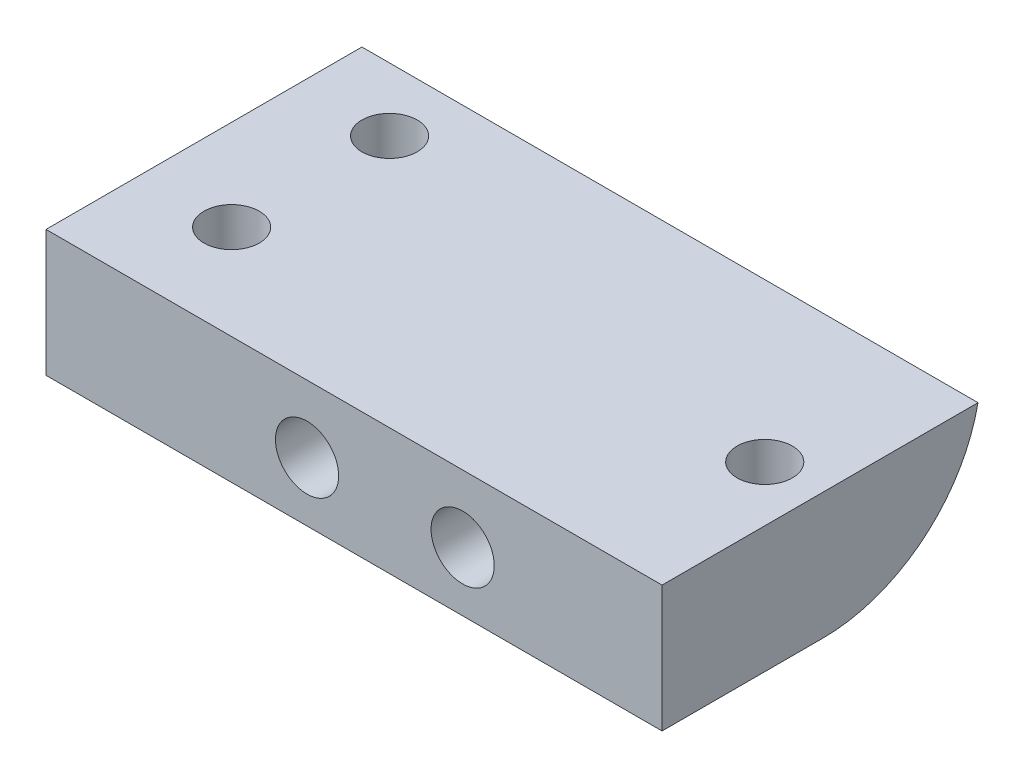
SolidWorks part; units mm, degrees
ref_plane "Front Plane" through (0, 0, 0) normal (0, 0, 1) x (1, 0, 0)
ref_plane "Top Plane" through (0, 0, 0) normal (0, 1, 0) x (1, 0, 0)
ref_plane "Right Plane" through (0, 0, 0) normal (1, 0, 0) x (0, 0, -1)
sketch "Sketch1" plane through (0, 0, 0) normal (0, 0, 1) x (1, 0, 0)
  line L1 (-6.6353, 11.7979) -> (32.3647, 11.7979)
  line L2 (-6.6353, 11.7979) -> (-6.6353, 3.7979)
  line L3 (-6.6353, 3.7979) -> (32.3647, 3.7979)
  line L4 (32.3647, 11.7979) -> (32.3647, 3.7979)
  circle A0 centre (9.8897, 7.5479) radius 2
  circle A1 centre (19.7397, 7.5479) radius 2
  dimension "D1" = 4
  dimension "D3" = 9.85
  dimension "D2" = 39
  dimension "D4" = 8
  dimension "D5" = 4.25
  dimension "D6" = 12.625
extrude "Boss-Extrude1" add sketch "Sketch1" along normal blind 20
sketch "Sketch2" plane through (0, 11.7979, 0) normal (0, 1, 0) x (1, 0, 0)
  line L0 (32.3647, -20) -> (-6.6353, -20) construction
  line L1 (-6.6353, -20) -> (-6.6353, 0) construction
  line L2 (32.3647, -20) -> (32.3647, 0) construction
  circle A0 centre (28.8647, -10) radius 1.75
  circle A1 centre (-0.8853, -14) radius 1.75
  circle A2 centre (-0.8853, -4) radius 1.75
  dimension "D2" = 3.5
  dimension "D3" = 6
  dimension "D1" = 10
  dimension "D4" = 10
  dimension "D5" = 5.75
  dimension "D6" = 3.5
extrude "Cut-Extrude3" cut sketch "Sketch2" against normal up to next
fillet "Fillet1" radius 10 1 edges at (12.8647, 3.7979, 0)
sketch "Sketch3" plane through (0, 3.7979, 0) normal (0, -1, 0) x (1, 0, 0)
  circle A0 centre (-0.8853, 14) radius 3.1
  circle A1 centre (28.8647, 10) radius 3.1
  circle A2 centre (-0.8853, 4) radius 3.1
  dimension "D1" = 6.2
extrude "Cut-Extrude4" cut sketch "Sketch3" against normal blind 4
